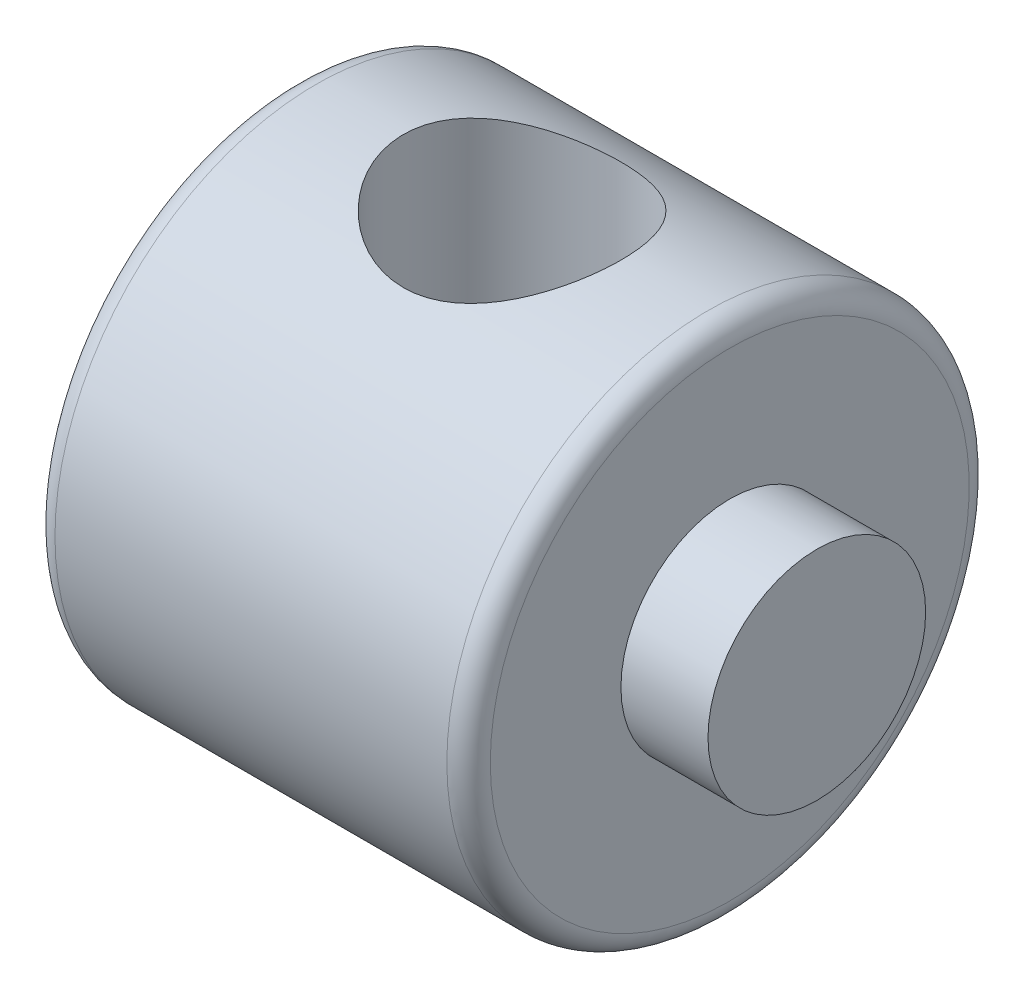
SolidWorks part; units mm, degrees
material "Alloy Steel"
ref_plane "Front Plane" through (0, 0, 0) normal (0, 0, 1) x (1, 0, 0)
ref_plane "Top Plane" through (0, 0, 0) normal (0, 1, 0) x (1, 0, 0)
ref_plane "Right Plane" through (0, 0, 0) normal (1, 0, 0) x (0, 0, -1)
sketch "Sketch1" plane through (0, 0, 0) normal (0, 0, 1) x (1, 0, 0)
  line L0 (-11.1125, 0) -> (-11.1125, 3.9688)
  line L1 (-11.1125, 3.9688) -> (-7.9375, 3.9688)
  line L2 (-7.9375, 3.9688) -> (-7.9375, 9.525)
  line L3 (-7.9375, 9.525) -> (7.9375, 9.525)
  line L4 (7.9375, 9.525) -> (7.9375, 3.9688)
  line L5 (7.9375, 3.9688) -> (11.1125, 3.9688)
  line L6 (11.1125, 3.9688) -> (11.1125, 0)
  line L7 (11.1125, 0) -> (-11.1125, 0)
  line L8 (-58.3897, 0) -> (112.59, 0) construction
  dimension "D1" = 22.225
  dimension "D2" = 3.175
  dimension "D3" = 19.05
  dimension "D4" = 7.9375
revolve "Revolve1" add sketch "Sketch1" angle 360 about L8
fillet "Fillet1" radius 0.7925 2 edges at (-7.9375, 0, 9.525) (7.9375, 0, 9.525)
hole_wizard "3/8-16 Tapped Hole1" positions "3DSketch1" profile "Sketch2" tap size "3/8-16" standard "Ansi Inch" end condition through all
sketch3d "3DSketch1"
  point P0 (0, 9.525, 0)
sketch "Sketch2" plane through (0, 9.525, 0) normal (1, 0, 0) x (0, 0, 1)
  line L0 (0, 0) -> (0, 19.05)
  line L1 (0, 19.05) -> (3.9687, 19.05)
  line L2 (3.9687, 19.05) -> (3.9687, 0)
  line L5 (3.9687, 0) -> (0, 0)
  line L11 (0, -6.35) -> (0, 107.95) construction
  dimension "Thru Tap Drill Dia." = 7.9375
  dimension "Thru Tap Drill Depth" = 19.05
cosmetic thread "Hole Thread1"
